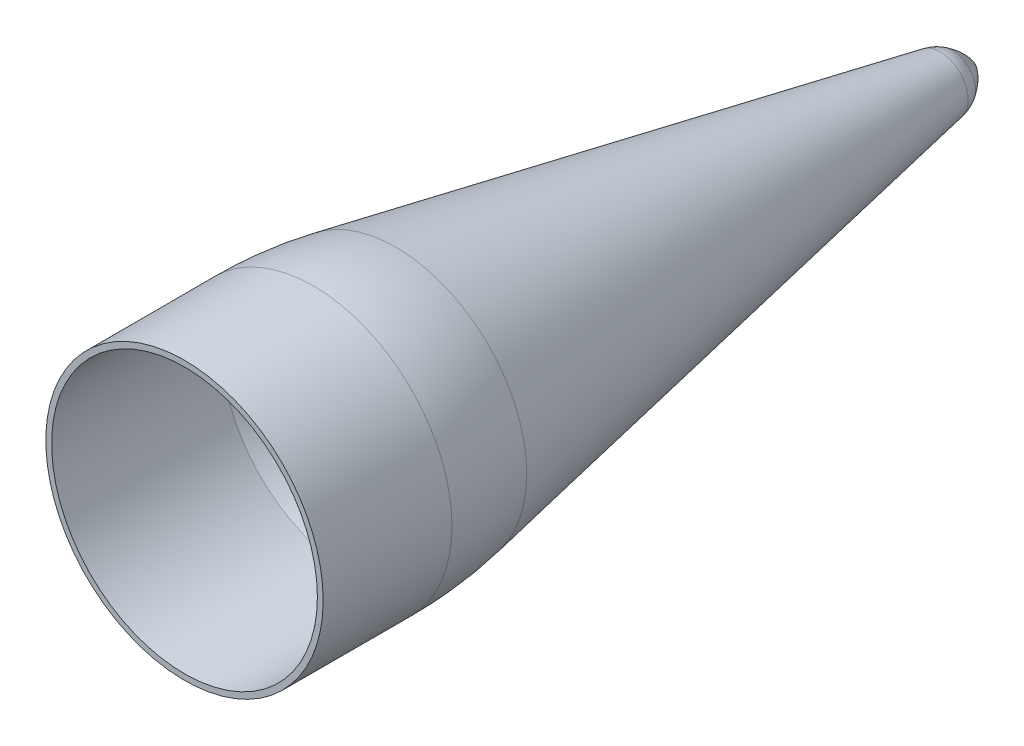
SolidWorks part; units mm, degrees
material "6061-T6 (SS)"
ref_plane "Front Plane" through (0, 0, 0) normal (0, 0, 1) x (1, 0, 0)
ref_plane "Top Plane" through (0, 0, 0) normal (0, 1, 0) x (1, 0, 0)
ref_plane "Right Plane" through (0, 0, 0) normal (1, 0, 0) x (0, 0, -1)
sketch "Sketch3" plane through (0, 0, 0) normal (0, 1, 0) x (1, 0, 0)
  line L0 (0, 20.6182) -> (0, 138.1781) construction
  line L1 (79.375, 0) -> (79.375, 97.5665)
  line L4 (0, 0) -> (79.375, 0)
  line L5 (0, 0) -> (0, 431.8)
  line L7 (15.415, 435.5939) -> (79.375, 97.5665)
  line L9 (0, 452.3407) -> (0, 431.8)
  arc A0 (15.415, 435.5939) -> (0, 452.3407) centre (-18.2733, 420.0526) ccw
  point P9 (9.0235, 445.1786)
  dimension "D1" = 79.375
  dimension "D2" = 431.8
  dimension "D3" = 15.875
revolve "Revolve1" add sketch "Sketch3" angle 360 about L0
shell "Shell1" thickness 3.302 removed face at (79.375, 0, 0)
fillet "Fillet1" radius 254 1 edges at (79.375, 0, -97.5665)
fillet "Fillet2" radius 20.32 1 edges at (15.415, 0, -435.5939)
